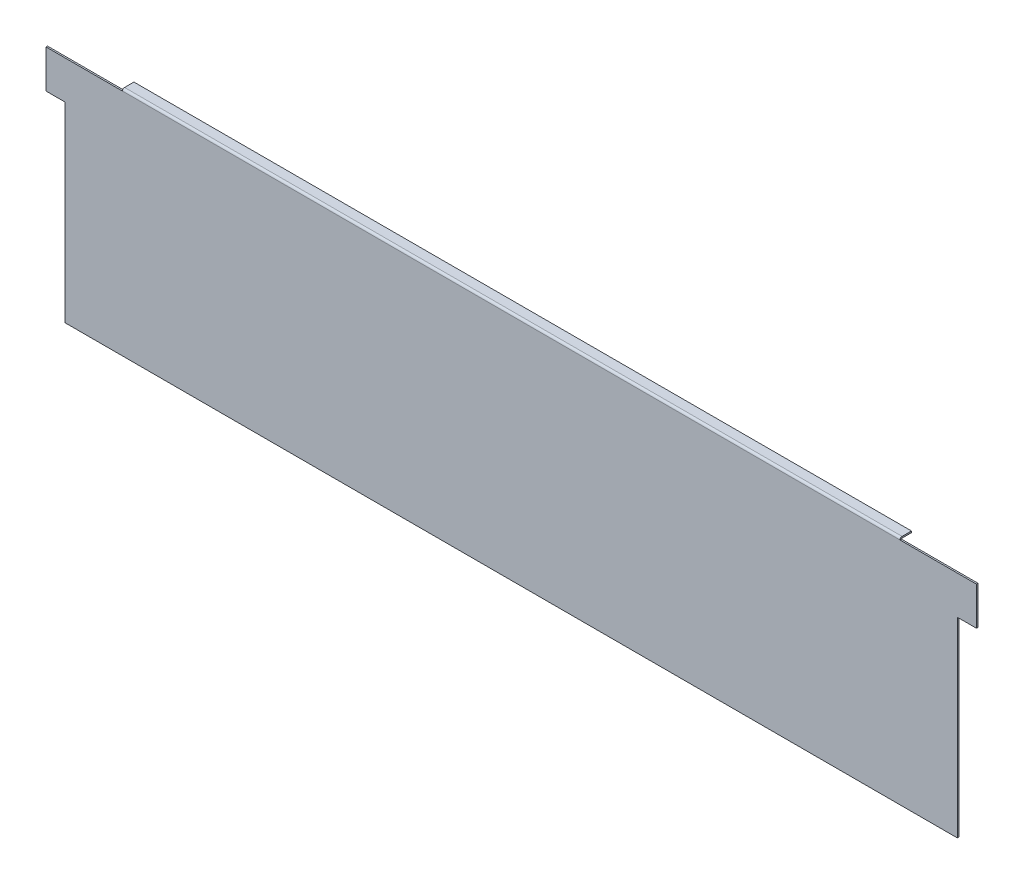
SolidWorks part; units mm, degrees
note: The reader was unsure of these and kept them because the rebuilt part matched: flange length of "Edge-Flange1".
ref_plane "Front Plane" through (0, 0, 0) normal (0, 0, 1) x (1, 0, 0)
ref_plane "Top Plane" through (0, 0, 0) normal (0, 1, 0) x (1, 0, 0)
ref_plane "Right Plane" through (0, 0, 0) normal (1, 0, 0) x (0, 0, -1)
sketch "Sketch1" plane through (0, 0, 0) normal (0, 0, 1) x (1, 0, 0)
  line L0 (960.4168, 91.4559) -> (985.4168, 91.4559)
  line L1 (-231.5832, 141.4559) -> (985.4168, 141.4559)
  line L2 (-231.5832, 141.4559) -> (-231.5832, 91.4559)
  line L3 (-231.5832, 91.4559) -> (-206.5832, 91.4559)
  line L4 (985.4168, 141.4559) -> (985.4168, 91.4559)
  line L6 (-206.5832, 91.4559) -> (-206.5832, -158.5441)
  line L7 (-206.5832, -158.5441) -> (960.4168, -158.5441)
  line L8 (960.4168, 91.4559) -> (960.4168, -158.5441)
  dimension "D1" = 1217
  dimension "D2" = 50
  dimension "D3" = 250
  dimension "D4" = 25
  dimension "D5" = 25
base flange "Base-Flange1" sketch "Sketch1" thickness 2 reverse thickness direction no parameters "D1"=0.7366
edge flange "Edge-Flange1" sketch "Sketch5" flange angle 90 flange length 15 flange position bend outside bend radius 0.7366 thickness 2 relief rectangular parameters "D6"=10
sketch "Sketch5" plane through (0, 141.4559, -2) normal (0, 1, 0) x (1, 0, 0)
  line L2 (-131.5832, 0) -> (-131.5832, 13)
  line L3 (-131.5832, 13) -> (885.4168, 13)
  line L4 (885.4168, 13) -> (885.4168, 0)
  line L7 (985.4168, 0) -> (-231.5832, 0) construction
  line L8 (885.4168, 0) -> (-131.5832, 0)
  line L11 (-231.5832, 0) -> (-231.5832, -2) construction
  line L12 (985.4168, 0) -> (985.4168, -2) construction
  point P4 (0, -2)
  point P7 (686.2375, -2)
  point P9 (-12.7934, -2)
  dimension "D1" = 100
  dimension "D2" = 100
bend "EdgeBend1" bend radius 0.7366 bend angle 90 parameters "D5"=1
sketch "Bend-Lines1" [suppressed] plane through (0, 0, 0) normal (0, 1, 0) x (1, 0, 0)
sketch "Bounding-Box1" [suppressed] plane through (0, 0, 0) normal (0, 1, 0) x (1, 0, 0)
sheet metal parameters "Sheet-Metal1" thickness 2 parameters "D1"=0.7366
flat pattern "Flat-Pattern1" [suppressed]
sketch "Bend-Lines2" plane through (0, 0, 0) normal (0, 1, 0) x (1, 0, 0)
sketch3d "Bounding-Box2" [suppressed]
  line L0 (-231.5832, -108.5441, 0) -> (985.4168, -108.5441, 0) construction
  line L1 (-231.5832, 141.4559, 0) -> (985.4168, 141.4559, 0) construction
  line L2 (-231.5832, -108.5441, 0) -> (-231.5832, 141.4559, 0) construction
  line L3 (985.4168, -108.5441, 0) -> (985.4168, 141.4559, 0) construction
sheet metal parameters "Sheet-Metal2" thickness 2 parameters "D1"=0.7366
flat pattern "Flat-Pattern1"
sketch "Bend-Lines2" plane through (0, 0, 0) normal (0, 0, 1) x (1, 0, 0)
  line L0 (885.4168, 142.8198) -> (-131.5832, 142.8198) construction
  line L1 (885.4168, 142.8198) -> (-131.5832, 142.8198) construction
sketch3d "Bounding-Box2" [suppressed]
  line L0 (-231.5832, -158.5441, 0) -> (985.4168, -158.5441, 0) construction
  line L1 (-231.5832, 156.4471, 0) -> (985.4168, 156.4471, 0) construction
  line L2 (-231.5832, -158.5441, 0) -> (-231.5832, 156.4471, 0) construction
  line L3 (985.4168, -158.5441, 0) -> (985.4168, 156.4471, 0) construction
bend of the flat pattern "Flatten-<EdgeBend1>1"
